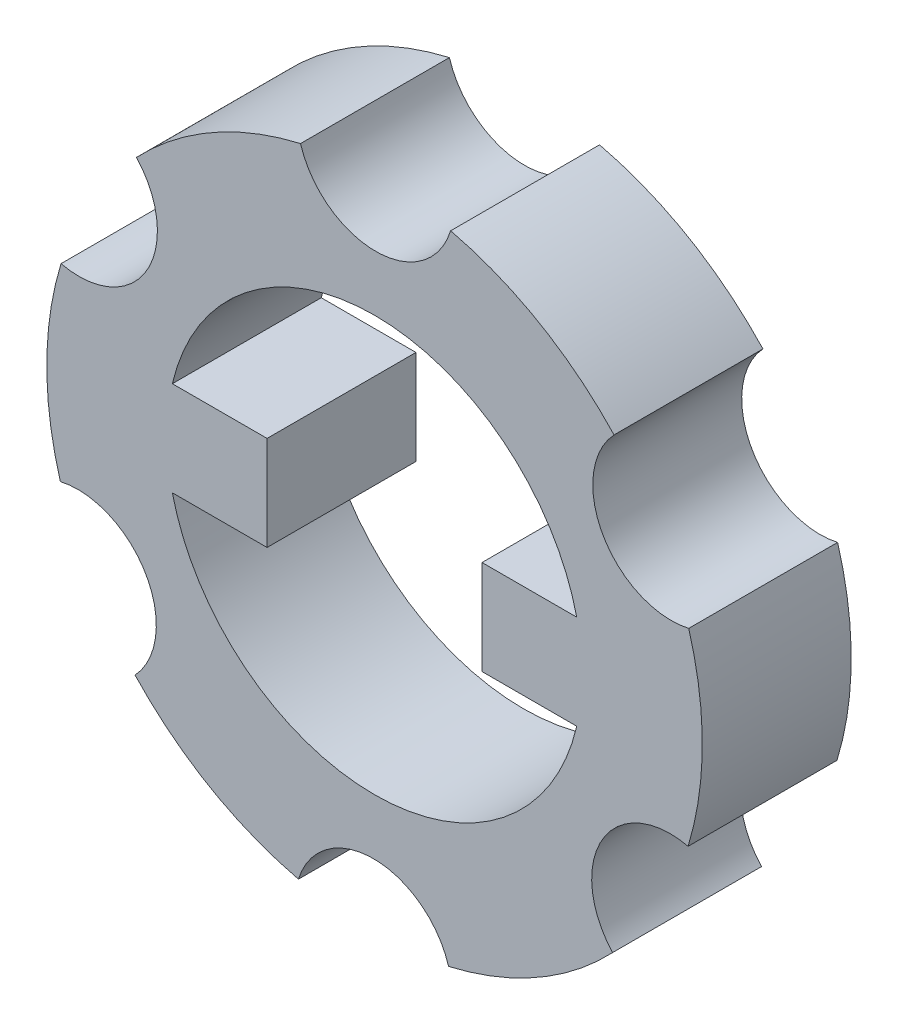
SolidWorks part; units mm, degrees
ref_plane "Front Plane" through (0, 0, 0) normal (0, 0, 1) x (1, 0, 0)
ref_plane "Top Plane" through (0, 0, 0) normal (0, 1, 0) x (1, 0, 0)
ref_plane "Right Plane" through (0, 0, 0) normal (1, 0, 0) x (0, 0, -1)
sketch "Sketch3" plane through (0, 0, 0) normal (0, 0, 1) x (1, 0, 0)
  circle A0 centre (0, 0) radius 21
  dimension "D1" = 42
extrude "Boss-Extrude3" add sketch "Sketch3" along normal blind 32
sketch "Sketch4" plane through (0, 0, 32) normal (0, 0, 1) x (1, 0, 0)
  circle A0 centre (0, 0) radius 19.3127
  circle A1 centre (0, 0) radius 21
extrude "Cut-Extrude1" cut sketch "Sketch4" against normal blind 28 from offset 2 offset against normal yes
ref_plane "Plane2" through (0, 0, 16) normal (0, 0, -1) x (-1, 0, 0)
ref_plane "Plane3" through (0, 0, 0) normal (0, 1, 0) x (1, 0, 0)
sketch "Sketch7" plane through (0, 0, 0) normal (0, 1, 0) x (1, 0, 0)
  line L0 (-19.3127, -2) -> (-19.3127, -30)
  arc A2 (-19.3127, -2) -> (-19.3127, -30) centre (-63.469, -16) cw
ref_axis "Axis1" through (0, 0, 2) along (0, 0, 1)
sweep "Cut-Sweep1" cut profiles "Sketch7" path edge at (19.3127, 0, 2)
sketch "Sketch8" plane through (0, 0, 0) normal (0, 0, -1) x (-1, 0, 0)
  line L0 (0, 6.075) -> (0, 17) construction
  line L1 (-4.6154, 10.5) -> (4.5477, 10.5) construction
  line L2 (17.6, 0) -> (-17.6, 0) construction
  circle A0 centre (0, 0) radius 6.075
  circle A1 centre (9.0763, 5.2793) radius 2.4097
  circle A2 centre (-0.0339, 10.5) radius 2.4097
  circle A3 centre (0, 0) radius 17 construction
  circle A4 centre (9.1102, -5.2207) radius 2.4097
  circle A5 centre (0.0339, -10.5) radius 2.4097
  circle A6 centre (-9.0763, -5.2793) radius 2.4097
  circle A7 centre (-9.1102, 5.2207) radius 2.4097
  dimension "D1" = 12.15
  dimension "D3" = 34
  dimension "D2" = 10.5
  dimension "D4" = 6
extrude "Cut-Extrude2" cut sketch "Sketch8" against normal through all contours A7 | A2 | A1 | A4 | A5 | A6 | A0
sketch "Sketch9" plane through (0, 0, 0) normal (0, 0, -1) x (-1, 0, 0)
  circle A0 centre (0, 0) radius 17
  circle A1 centre (0, 0) radius 4
  dimension "D1" = 34
sketch "Sketch10" plane through (0, 0, 0) normal (0, 1, 0) x (1, 0, 0)
  line L0 (-6.075, 0) -> (-15.2418, -2.7958)
  line L1 (-15.2418, -2.7958) -> (-19.075, 0)
  line L2 (17, 0) -> (-17, 0) construction
  line L3 (21, 0) -> (-21, 0) construction
  line L4 (-19.075, 0) -> (-6.075, 0)
  dimension "D1" = 13
revolve "Cut-Revolve1" cut sketch "Sketch10" angle 360 about axis through (0, 0, 2) along (0, 0, 1)
fillet "Fillet1" radius 1 2 edges at (21, 0, 30) (21, 0, 2)
fillet "Fillet3" radius 5 1 edges at (-15.2418, 0, 2.7958)
sketch "Sketch11" plane through (0, 0, 32) normal (0, 0, 1) x (1, 0, 0)
  circle A0 centre (0, 0) radius 8
  dimension "D1" = 16
extrude "Boss-Extrude4" add sketch "Sketch11" against normal blind 15 from offset 17 offset against normal yes
sketch "Sketch12" plane through (0, 0, 32) normal (0, 0, 1) x (1, 0, 0)
  line L0 (-3, -1.75) -> (-9.25, -1.75)
  line L1 (9.25, 1.75) -> (3, 1.75)
  line L2 (9.25, 1.75) -> (9.25, -1.75)
  line L3 (9.25, -1.75) -> (3, -1.75)
  line L4 (-9.25, 1.75) -> (-9.25, -1.75)
  line L5 (-3, 1.75) -> (-9.25, 1.75)
  line L8 (-3, 1.75) -> (-3, -1.75)
  line L10 (3, 1.75) -> (3, -1.75)
  point P0 (0, 0)
  point P6 (0, 0)
  dimension "D1" = 18.5
  dimension "D2" = 3.5
extrude "Boss-Extrude5" add sketch "Sketch12" against normal up to surface (17 mm away) up to face at (6.075, 0, 15)
sketch "Sketch15" plane through (0, 0, 32) normal (0, 0, 1) x (1, 0, 0)
  line L28 (-6.2079, 1.45) -> (-3.3, 1.45)
  line L29 (-3.3, 1.45) -> (-3.3, -1.45)
  line L30 (-3.3, -1.45) -> (-6.2079, -1.45)
  line L31 (6.2079, -1.45) -> (3.3, -1.45)
  line L32 (3.3, -1.45) -> (3.3, 1.45)
  line L33 (3.3, 1.45) -> (6.2079, 1.45)
  line L34 (-6.2079, 1.45) -> (-3.3, 1.45)
  line L35 (-3.3, 1.45) -> (-3.3, -1.45)
  line L36 (-3.3, -1.45) -> (-6.2079, -1.45)
  line L37 (6.2079, -1.45) -> (3.3, -1.45)
  line L38 (3.3, -1.45) -> (3.3, 1.45)
  line L39 (3.3, 1.45) -> (6.2079, 1.45)
  circle A5 centre (0, 0) radius 21
  circle A6 centre (0, 0) radius 21
  arc A10 (-6.2079, -1.45) -> (6.2079, -1.45) centre (0, 0) ccw
  arc A11 (6.2079, 1.45) -> (-6.2079, 1.45) centre (0, 0) ccw
  arc A12 (-6.2079, -1.45) -> (6.2079, -1.45) centre (0, 0) ccw
  arc A13 (6.2079, 1.45) -> (-6.2079, 1.45) centre (0, 0) ccw
  dimension "D1" = 0
  dimension "D2" = 0.3
extrude "Cut-Extrude3" cut sketch "Sketch15" against normal up to surface (17 mm away) flip side to cut up to face at (0, 0, 15)
sketch "Sketch16" plane through (0, 0, 32) normal (0, 0, 1) x (1, 0, 0)
  circle A0 centre (0, 0) radius 25.9992
  circle A1 centre (0, 0) radius 10.0631
extrude "Cut-Extrude4" cut sketch "Sketch16" against normal through all
sketch "Sketch17" plane through (0, 0, 0) normal (0, 1, 0) x (1, 0, 0)
  line L1 (18.941, -27.4283) -> (-15.1846, -27.4283)
  line L2 (18.941, -27.4283) -> (18.941, 0.7763)
  line L3 (18.941, 0.7763) -> (-15.1846, 0.7763)
  line L4 (-15.1846, -27.4283) -> (-15.1846, 0.7763)
  line L5 (18.941, -27.4283) -> (-15.1846, 0.7763) construction
  line L6 (18.941, 0.7763) -> (-15.1846, -27.4283) construction
  point P4 (1.8782, -13.326)
extrude "Cut-Extrude5" cut sketch "Sketch17" against normal through all and the other way through all
